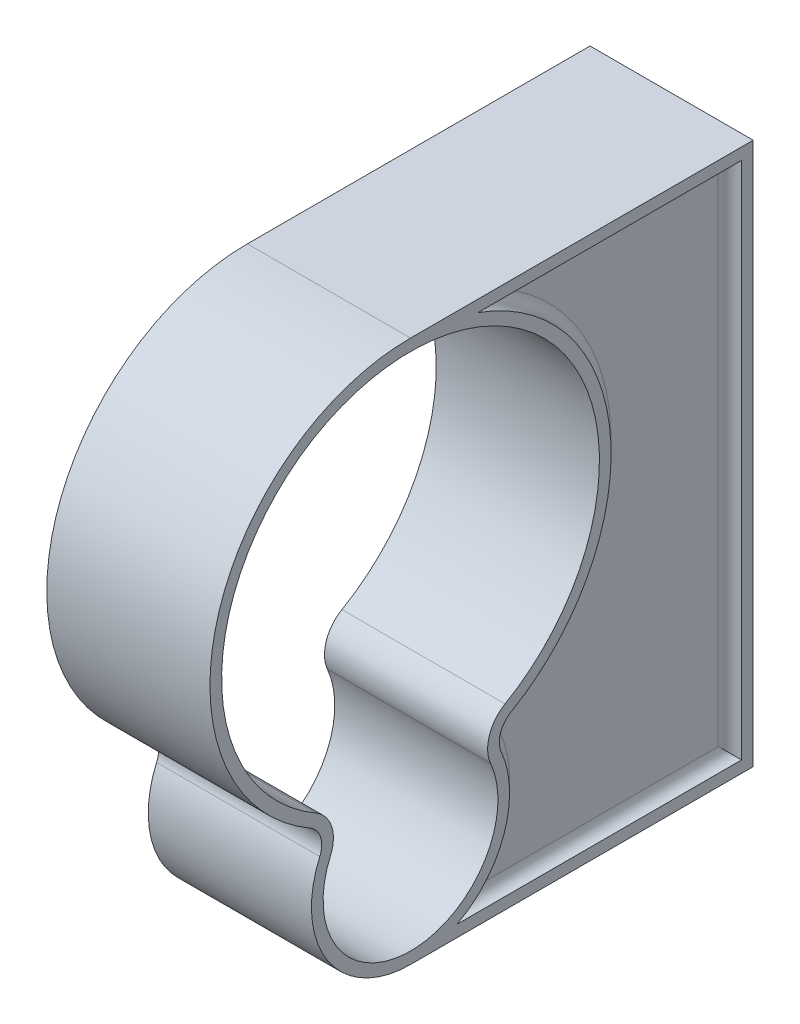
SolidWorks part; units mm, degrees
ref_plane "Front Plane" through (0, 0, 0) normal (0, 0, 1) x (1, 0, 0)
ref_plane "Top Plane" through (0, 0, 0) normal (0, 1, 0) x (1, 0, 0)
ref_plane "Right Plane" through (0, 0, 0) normal (1, 0, 0) x (0, 0, -1)
sketch "Sketch1" plane through (0, 0, 0) normal (1, 0, 0) x (0, 0, -1)
  line L1 (0, -120.6658) -> (293.9982, -120.6658)
  line L2 (0, 344.7979) -> (293.9982, 344.7979)
  line L3 (293.9982, -120.6658) -> (293.9982, 344.7979)
  arc A0 (81.1531, 32.4379) -> (-81.1531, 32.4379) centre (0, 172.7272) ccw
  arc A1 (-68.6963, -5.569) -> (68.6963, -5.569) centre (0, -35.6658) ccw
  arc A2 (68.6963, -5.569) -> (81.1531, 32.4379) centre (96.1749, 6.4697) cw
  arc A3 (-68.6963, -5.569) -> (-81.1531, 32.4379) centre (-96.1749, 6.4697) ccw
  arc A4 (0, 344.7979) -> (-86.1603, 23.7818) centre (0, 172.7272) ccw
  arc A5 (-77.8558, -1.5561) -> (-86.1603, 23.7818) centre (-96.1749, 6.4697) ccw
  arc A6 (-77.8558, -1.5561) -> (0, -120.6658) centre (0, -35.6658) ccw
  arc A8 (-77.8558, -1.5561) -> (77.8558, -1.5561) centre (0, -35.6658) ccw construction
  arc A9 (77.8558, -1.5561) -> (86.1603, 23.7818) centre (96.1749, 6.4697) cw construction
  arc A10 (86.1603, 23.7818) -> (-86.1603, 23.7818) centre (0, 172.7272) ccw construction
  dimension "D1" = 324.1414
  dimension "D2" = 150
  dimension "D4" = 30
  dimension "D3" = 208.393
  dimension "D5" = 10
extrude "Boss-Extrude1" add sketch "Sketch1" along normal blind 140
sketch "Sketch2" plane through (0, 0, -293.9982) normal (0, 0, -1) x (-1, 0, 0)
  line L8 (-30, -90.6658) -> (-30, 314.7979)
  line L9 (-30, 314.7979) -> (-110, 314.7979)
  line L10 (-110, 314.7979) -> (-110, -90.6658)
  line L11 (-110, -90.6658) -> (-30, -90.6658)
  line L12 (-30, -75.6658) -> (-30, 299.7979)
  line L13 (-45, 314.7979) -> (-95, 314.7979)
  line L14 (-110, 299.7979) -> (-110, -75.6658)
  line L15 (-95, -90.6658) -> (-45, -90.6658)
  circle A0 centre (-110, 314.7979) radius 15
  circle A1 centre (-30, 314.7979) radius 15
  circle A2 centre (-30, -90.6658) radius 15
  circle A3 centre (-110, -90.6658) radius 15
  dimension "D2" = 30
  dimension "D1" = 30
extrude "Cut-Extrude1" cut sketch "Sketch2" against normal blind 140 contours A0 | A2 | A3 | A1
sketch "Sketch3" plane through (140, 0, 0) normal (1, 0, 0) x (0, 0, -1)
  line L6 (0, -110.6658) -> (283.9982, -110.6658)
  line L7 (283.9982, -110.6658) -> (283.9982, 334.7979)
  line L8 (283.9982, 334.7979) -> (0, 334.7979)
  line L9 (40, -110.6658) -> (283.9982, -110.6658)
  line L10 (283.9982, -110.6658) -> (283.9982, 334.7979)
  line L11 (283.9982, 334.7979) -> (57.805, 334.7979)
  arc A6 (-68.6963, -5.569) -> (-81.1531, 32.4379) centre (-96.1749, 6.4697) ccw
  arc A7 (-68.6963, -5.569) -> (0, -110.6658) centre (0, -35.6658) ccw
  arc A8 (0, 334.7979) -> (-81.1531, 32.4379) centre (0, 172.7272) ccw
  arc A15 (-77.8558, -1.5561) -> (77.8558, -1.5561) centre (0, -35.6658) ccw
  arc A16 (86.1603, 23.7818) -> (77.8558, -1.5561) centre (96.1749, 6.4697) ccw
  arc A17 (86.1603, 23.7818) -> (-86.1603, 23.7818) centre (0, 172.7272) ccw
  arc A18 (40, -110.6658) -> (77.8558, -1.5561) centre (0, -35.6658) ccw
  arc A19 (86.1603, 23.7818) -> (77.8558, -1.5561) centre (96.1749, 6.4697) ccw
  arc A20 (86.1603, 23.7818) -> (57.805, 334.7979) centre (0, 172.7272) ccw
  dimension "D1" = 10
  dimension "D2" = 10
extrude "Cut-Extrude2" cut sketch "Sketch3" against normal blind 10
sketch "Sketch4" plane through (0, 0, 0) normal (-1, 0, 0) x (0, 0, 1)
  line L6 (0, 334.7979) -> (-283.9982, 334.7979)
  line L7 (-283.9982, 334.7979) -> (-283.9982, -110.6658)
  line L8 (-283.9982, -110.6658) -> (0, -110.6658)
  line L9 (-57.805, 334.7979) -> (-283.9982, 334.7979)
  line L10 (-283.9982, 334.7979) -> (-283.9982, -110.6658)
  line L11 (-283.9982, -110.6658) -> (-40, -110.6658)
  arc A6 (81.1531, 32.4379) -> (68.6963, -5.569) centre (96.1749, 6.4697) ccw
  arc A7 (81.1531, 32.4379) -> (0, 334.7979) centre (0, 172.7272) ccw
  arc A8 (0, -110.6658) -> (68.6963, -5.569) centre (0, -35.6658) ccw
  arc A15 (-77.8558, -1.5561) -> (77.8558, -1.5561) centre (0, -35.6658) ccw
  arc A16 (-77.8558, -1.5561) -> (-86.1603, 23.7818) centre (-96.1749, 6.4697) ccw
  arc A17 (86.1603, 23.7818) -> (-86.1603, 23.7818) centre (0, 172.7272) ccw
  arc A18 (-77.8558, -1.5561) -> (-40, -110.6658) centre (0, -35.6658) ccw
  arc A19 (-77.8558, -1.5561) -> (-86.1603, 23.7818) centre (-96.1749, 6.4697) ccw
  arc A20 (-57.805, 334.7979) -> (-86.1603, 23.7818) centre (0, 172.7272) ccw
  dimension "D1" = 10
  dimension "D2" = 10
extrude "Cut-Extrude3" cut sketch "Sketch4" against normal blind 10
fillet "Fillet1" radius 10 12 edges at (130, 334.7979, -170.9016) (130, 112.0661, -283.9982) (130, -110.6658, -161.9991) (130, -63.5274, -80.304) (130, 12.6987, -77.1696) (130, 188.3501, -171.36) (10, 12.6987, -77.1696) (10, -63.5274, -80.304) (10, -110.6658, -161.9991) (10, 112.0661, -283.9982) (10, 334.7979, -170.9016) (10, 188.3501, -171.36)
